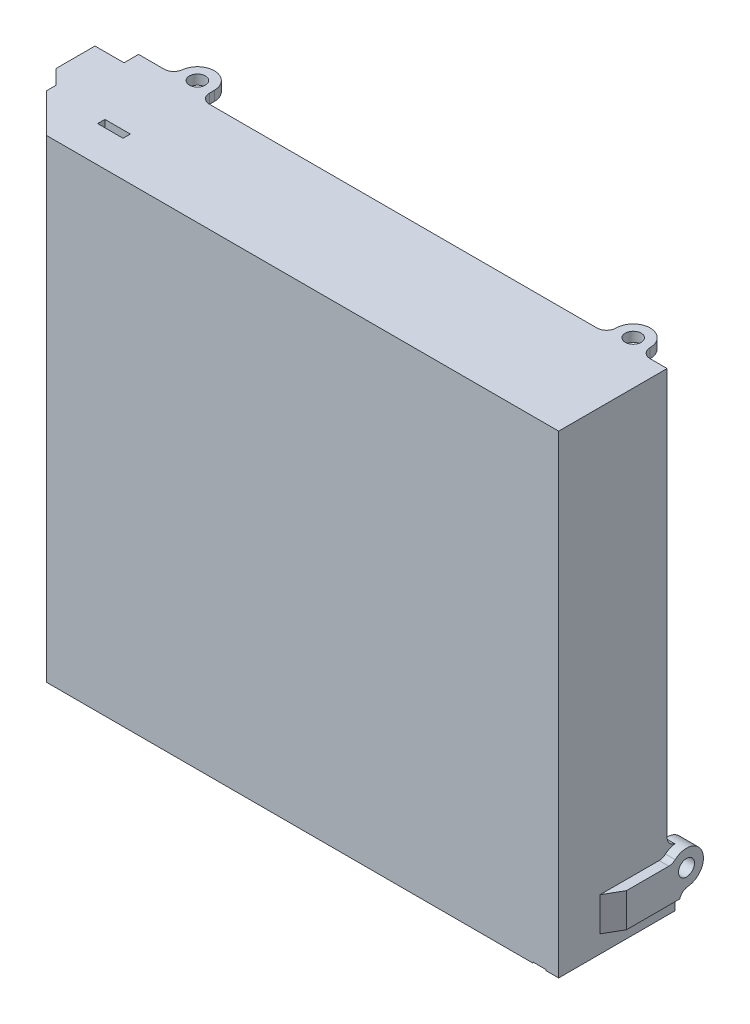
SolidWorks part; units mm, degrees
ref_plane "前视基准面" through (0, 0, 0) normal (0, 0, 1) x (1, 0, 0)
ref_plane "上视基准面" through (0, 0, 0) normal (0, 1, 0) x (1, 0, 0)
ref_plane "右视基准面" through (0, 0, 0) normal (1, 0, 0) x (0, 0, -1)
other "Configuration Table"
sketch "草图1" plane through (0, 0, 0) normal (0, 1, 0) x (1, 0, 0)
  line L1 (0, 0) -> (114.75, 0)
  line L2 (0, 0) -> (0, 22)
  line L3 (0, 22) -> (114.75, 22)
  line L4 (114.75, 0) -> (114.75, 22)
  line L5 (0, 0) -> (114.75, 22) construction
  line L6 (0, 22) -> (114.75, 0) construction
  point P4 (57.375, 11)
  dimension "D1" = 114.75
  dimension "D2" = 22
extrude "凸台-拉伸1" add sketch "草图1" along normal blind 2
sketch "草图2" plane through (0, 2, 0) normal (0, 1, 0) x (1, 0, 0)
  line L0 (16.75, 23.4) -> (16.75, 22) construction
  line L1 (114.75, 22) -> (0, 22) construction
  line L2 (0, 22) -> (0, 0) construction
  line L3 (0, 0) -> (114.75, 0) construction
  line L4 (20.25, 23.4) -> (20.25, 22)
  line L5 (13.25, 23.4) -> (13.25, 22)
  line L6 (107.75, 22) -> (107.75, 22.4) construction
  line L7 (104.25, 22) -> (104.25, 22.4)
  line L8 (111.25, 22) -> (111.25, 22.4)
  circle A0 centre (16.75, 23.4) radius 1.65
  arc A1 (20.25, 23.4) -> (13.25, 23.4) centre (16.75, 23.4) ccw
  arc A2 (13.25, 22) -> (20.25, 22) centre (16.75, 22) ccw
  arc A3 (104.25, 22) -> (111.25, 22) centre (107.75, 22) ccw
  arc A4 (111.25, 22.4) -> (104.25, 22.4) centre (107.75, 22.4) ccw
  circle A5 centre (107.75, 22.4) radius 1.65
  point P6 (16.75, 22.7)
  point P16 (107.75, 22.2)
  point P23 (107.6556, 23.4)
  point P24 (107.6398, 22.6248)
  dimension "D1" = 16.75
  dimension "D2" = 3.3
  dimension "D3" = 23.4
  dimension "D4" = 3.5
  dimension "D5" = 1
  dimension "D7" = 3.5
  dimension "D6" = 91
extrude "凸台-拉伸2" add sketch "草图2" against normal up to surface (2 mm away) up to face at (57.375, 0, -11)
sketch "草图3" plane through (0, 2, 0) normal (0, 1, 0) x (1, 0, 0)
  circle A0 centre (16.75, 23.4) radius 1.65
  circle A1 centre (107.75, 22.4) radius 1.65
extrude "切除-拉伸1" cut sketch "草图3" against normal blind 10
sketch "草图4" plane through (0, 0, 0) normal (0, -1, 0) x (1, 0, 0)
  line L0 (0, -22) -> (0, 0) construction
  line L1 (114.75, 0) -> (21.75, 0)
  line L2 (114.75, 0) -> (114.75, -17)
  line L3 (114.75, -17) -> (21.75, -17)
  line L4 (21.75, 0) -> (21.75, -17)
  line L5 (114.75, 0) -> (21.75, -17) construction
  line L6 (114.75, -17) -> (21.75, 0) construction
  point P4 (68.25, -8.5)
  dimension "D1" = 21.75
  dimension "D2" = 17
extrude "凸台-拉伸3" add sketch "草图4" along normal blind 1
sketch "草图5" plane through (0, 0, 0) normal (0, -1, 0) x (1, 0, 0)
  line L1 (0, -22) -> (6, -22)
  line L2 (0, -22) -> (0, -19)
  line L3 (0, -19) -> (6, -19)
  line L4 (6, -22) -> (6, -19)
  line L5 (0, -22) -> (6, -19) construction
  line L6 (0, -19) -> (6, -22) construction
  point P4 (3, -20.5)
  dimension "D1" = 3
  dimension "D2" = 6
extrude "切除-拉伸2" cut sketch "草图5" against normal up to next
sketch "草图6" plane through (0, 0, 0) normal (0, -1, 0) x (1, 0, 0)
  line L0 (0, 0) -> (21.75, 0) construction
  line L1 (14.15, -5.4) -> (19.4, -5.4)
  line L2 (14.15, -5.4) -> (14.15, -6.9)
  line L3 (14.15, -6.9) -> (19.4, -6.9)
  line L4 (19.4, -5.4) -> (19.4, -6.9)
  line L5 (14.15, -5.4) -> (19.4, -6.9) construction
  line L6 (14.15, -6.9) -> (19.4, -5.4) construction
  line L7 (0, -19) -> (0, 0) construction
  point P4 (16.775, -6.15)
  dimension "D1" = 6.9
  dimension "D2" = 1.5
  dimension "D3" = 14.15
  dimension "D4" = 5.25
extrude "切除-拉伸3" cut sketch "草图6" against normal up to next
sketch "草图7" plane through (0, 0, 0) normal (0, -1, 0) x (1, 0, 0)
  line L0 (14.15, -6.9) -> (19.4, -6.9) construction
  line L1 (21.75, 0) -> (16.75, 0)
  line L2 (21.75, 0) -> (21.75, -17)
  line L3 (21.75, -17) -> (16.75, -17)
  line L4 (16.75, 0) -> (16.75, -5.4)
  line L5 (21.75, 0) -> (16.75, -17) construction
  line L6 (21.75, -17) -> (16.75, 0) construction
  line L7 (19.4, -6.9) -> (19.4, -5.4) construction
  line L8 (19.4, -5.4) -> (14.15, -5.4) construction
  line L9 (16.75, -6.9) -> (19.4, -6.9)
  line L10 (19.4, -6.9) -> (19.4, -5.4)
  line L11 (19.4, -5.4) -> (16.75, -5.4)
  line L12 (16.75, -6.9) -> (16.75, -17)
  point P4 (19.25, -8.5)
  point P6 (21.75, -17)
  dimension "D1" = 5
extrude "凸台-拉伸4" add sketch "草图7" along normal blind 0.5
sketch "草图8" plane through (0, 0, 0) normal (0, -1, 0) x (1, 0, 0)
  line L1 (0, 0) -> (3, 0)
  line L2 (0, 0) -> (0, -10.9)
  line L3 (0, -10.9) -> (3, -10.9)
  line L4 (3, 0) -> (3, -10.9)
  line L5 (0, 0) -> (3, -10.9) construction
  line L6 (0, -10.9) -> (3, 0) construction
  line L7 (6, -19) -> (0, -19) construction
  point P4 (1.5, -5.45)
  dimension "D1" = 8.1
  dimension "D2" = 3
extrude "切除-拉伸4" cut sketch "草图8" against normal up to next
chamfer "倒角1" distance 3 angle 45 1 edges at (3, 1, -10.9)
chamfer "倒角2" distance 6 angle 45 1 edges at (3, 1, 0)
sketch "草图9" plane through (114.75, 0, 0) normal (1, 0, 0) x (0, 0, -1)
  line L1 (0, 2) -> (22, 2)
  line L2 (0, 2) -> (0, -95.8)
  line L3 (0, -95.8) -> (22, -95.8)
  line L4 (22, 2) -> (22, -95.8)
  line L5 (0, 2) -> (22, -95.8) construction
  line L6 (0, -95.8) -> (22, 2) construction
  point P4 (11, -46.9)
  point P6 (0, 0)
  point P8 (22, 2)
  dimension "D1" = 97.8
extrude "凸台-拉伸5" add sketch "草图9" along normal blind 2
sketch "草图10" plane through (0, 0, -17) normal (0, 0, -1) x (-1, 0, 0)
  line L1 (-114.75, 0) -> (-113.75, 0)
  line L2 (-114.75, 0) -> (-114.75, -95.8)
  line L3 (-114.75, -95.8) -> (-113.75, -95.8)
  line L4 (-113.75, 0) -> (-113.75, -95.8)
  line L5 (-114.75, 0) -> (-113.75, -95.8) construction
  line L6 (-114.75, -95.8) -> (-113.75, 0) construction
  point P4 (-114.25, -47.9)
  point P6 (-114.75, -95.8)
  dimension "D1" = 1
extrude "凸台-拉伸6" add sketch "草图10" against normal up to surface (17 mm away) up to face at (55.8, -19.06, 0)
fillet "圆角2" radius 3 1 edges at (114.75, 0, -19.5)
sketch "草图11" plane through (0, -95.8, 0) normal (0, -1, 0) x (1, 0, 0)
  line L0 (116.75, -22) -> (114.75, -22) construction
  line L1 (115.35, -22) -> (113.75, -22)
  line L2 (115.35, -22) -> (115.35, 0)
  line L3 (115.35, 0) -> (113.75, 0)
  line L4 (113.75, -22) -> (113.75, 0)
  line L5 (115.35, -22) -> (113.75, 0) construction
  line L6 (115.35, 0) -> (113.75, -22) construction
  line L7 (116.75, 0) -> (116.75, -22) construction
  point P4 (114.55, -11)
  dimension "D1" = 1.4
extrude "切除-拉伸6" cut sketch "草图11" against normal blind 1.6
sketch "草图12" plane through (113.75, 0, 0) normal (-1, 0, 0) x (0, 0, 1)
  line L1 (-19, -90.175) -> (-12, -90.175)
  line L2 (-19, -90.175) -> (-19, -87.175)
  line L3 (-19, -87.175) -> (-12, -87.175)
  line L4 (-12, -90.175) -> (-12, -87.175)
  line L5 (-19, -90.175) -> (-12, -87.175) construction
  line L6 (-19, -87.175) -> (-12, -90.175) construction
  line L7 (-22, -95.8) -> (0, -95.8) construction
  line L8 (-22, -94.2) -> (-22, -3) construction
  point P4 (-15.5, -88.675)
  dimension "D1" = 7.125
  dimension "D2" = 3
  dimension "D3" = 3
  dimension "D4" = 7
extrude "切除-拉伸7" cut sketch "草图12" against normal up to next
sketch "草图13" plane through (116.75, 0, 0) normal (1, 0, 0) x (0, 0, -1)
  line L0 (22, -95.8) -> (22, 2) construction
  line L1 (0, -95.8) -> (22, -95.8) construction
  line L2 (19, -87.175) -> (19, -90.175) construction
  line L3 (12, -87.175) -> (19, -87.175) construction
  line L4 (19, -87.175) -> (19, -88.1057)
  line L5 (18.9014, -87.175) -> (19, -87.175)
  circle A0 centre (22.4, -87.275) radius 1.65
  arc A1 (19, -88.1057) -> (18.9014, -87.175) centre (22.4, -87.275) ccw
  dimension "D1" = 3.3
  dimension "D2" = 0.4
  dimension "D3" = 7
  dimension "D4" = 8.525
extrude "凸台-拉伸7" add sketch "草图13" against normal up to surface (2 mm away) up to face at (114.75, -68.6375, -18.75)
sketch "草图14" plane through (116.75, 0, 0) normal (1, 0, 0) x (0, 0, -1)
  line L0 (12, -87.175) -> (19, -87.175) construction
  line L1 (21, -85.175) -> (10, -85.175)
  line L2 (21, -85.175) -> (21, -92.175)
  line L3 (21, -92.175) -> (10, -92.175)
  line L4 (10, -85.175) -> (10, -92.175)
  line L5 (21, -85.175) -> (10, -92.175) construction
  line L6 (21, -92.175) -> (10, -85.175) construction
  line L7 (19, -90.175) -> (12, -90.175) construction
  line L8 (12, -90.175) -> (12, -87.175) construction
  line L9 (19, -87.175) -> (19, -90.175) construction
  point P4 (15.5, -88.675)
  dimension "D1" = 2
  dimension "D2" = 2
  dimension "D3" = 2
  dimension "D4" = 2
extrude "凸台-拉伸8" add sketch "草图14" along normal blind 2
chamfer "倒角3" distance 2 angle 60 1 edges at (116.75, -88.675, -10) first distance on face at (117.75, -88.675, -10)
sketch "草图15" plane through (116.75, 0, 0) normal (1, 0, 0) x (0, 0, -1)
  circle A0 centre (22.4, -87.275) radius 1.65
  circle A1 centre (22.4, -87.275) radius 3.5
extrude "凸台-拉伸9" add sketch "草图15" along normal up to surface (2 mm away) up to face at (118.75, -88.675, -15.5)
sketch "草图16" plane through (118.75, 0, 0) normal (1, 0, 0) x (0, 0, -1)
  circle A0 centre (22.4, -87.275) radius 1.65
  arc A1 (21, -88.1482) -> (21, -86.4018) centre (22.4, -87.275) ccw construction
extrude "切除-拉伸8" cut sketch "草图16" against normal up to next
sketch "草图17" plane through (0, 0, -22) normal (0, 0, -1) x (-1, 0, 0)
  line L4 (-20.25, 2) -> (-104.25, 2)
  line L5 (-104.25, 2) -> (-104.25, 0)
  line L6 (-116.75, 2) -> (-116.75, -83.7979)
  line L7 (-116.75, -83.7979) -> (-114.75, -83.7979)
  line L8 (-114.75, -83.7979) -> (-114.75, -3)
  line L9 (-111.75, 0) -> (-111.25, 0)
  line L10 (-111.25, 0) -> (-111.25, 2)
  line L11 (-111.25, 2) -> (-116.75, 2)
  line L12 (-116.75, 2) -> (-116.75, -83.7979)
  line L13 (-116.75, -83.7979) -> (-114.75, -83.7979)
  line L14 (-114.75, -83.7979) -> (-114.75, -3)
  line L15 (-111.75, 0) -> (-111.25, 0)
  line L16 (-111.25, 0) -> (-111.25, 2)
  line L17 (-111.25, 2) -> (-116.75, 2)
  line L18 (-104.25, 0) -> (-20.25, 0)
  line L19 (-20.25, 0) -> (-20.25, 2)
  line L20 (-20.25, 2) -> (-104.25, 2)
  line L21 (-104.25, 2) -> (-104.25, 0)
  line L22 (-104.25, 0) -> (-20.25, 0)
  line L23 (-20.25, 0) -> (-20.25, 2)
  arc A1 (-111.75, 0) -> (-114.75, -3) centre (-111.75, -3) ccw
  arc A2 (-111.75, 0) -> (-114.75, -3) centre (-111.75, -3) ccw
  dimension "D1" = 0
  dimension "D2" = 0
extrude "切除-拉伸9" cut sketch "草图17" against normal blind 1.6
fillet "圆角3" radius 2 2 edges at (115.75, -90.7521, -22) (115.75, -83.7979, -20.4)
fillet "圆角4" radius 2 6 edges at (117.75, -85.175, -19.6) (117.75, -90.4828, -21) (20.25, 1, -20.4) (13.25, 1, -22) (104.25, 1, -20.4) (111.25, 1, -20.4)
sketch "草图18" plane through (0, 0, 0) normal (0, 0, 1) x (1, 0, 0)
  line L1 (9, 2) -> (116.75, 2)
  line L2 (9, 2) -> (9, -95.8)
  line L3 (9, -95.8) -> (116.75, -95.8)
  line L4 (116.75, 2) -> (116.75, -95.8)
  line L5 (9, 2) -> (116.75, -95.8) construction
  line L6 (9, -95.8) -> (116.75, 2) construction
  point P4 (62.875, -46.9)
extrude "凸台-拉伸10" add sketch "草图18" along normal blind 2
sketch "草图19" plane through (0, 2, 0) normal (0, 1, 0) x (1, 0, 0)
  line L0 (9, 0) -> (11, -2)
  line L1 (116.75, -2) -> (9, -2) construction
  line L2 (11, -2) -> (9, -2)
  line L3 (9, -2) -> (9, 0)
extrude "切除-拉伸10" cut sketch "草图19" against normal up to next
sketch "草图20" plane through (0, -94.2, 0) normal (0, -1, 0) x (1, 0, 0)
  line L0 (11, 2) -> (116.75, 2) construction
  line L1 (116.75, 2) -> (116.75, -22) construction
  circle A0 centre (112.75, -1.5) radius 1.25
  circle A1 centre (112.75, -1.5) radius 3.3
  dimension "D1" = 3.5
  dimension "D2" = 4
  dimension "D3" = 6.6
  dimension "D4" = 2.5
extrude "凸台-拉伸11" add sketch "草图20" against normal blind 5 from offset 1.5 offset against normal yes
sketch "草图21" plane through (0, -94.2, 0) normal (0, -1, 0) x (1, 0, 0)
  circle A0 centre (112.75, -1.5) radius 1.25
  arc A1 (113.75, -0.75) -> (113.75, -2.25) centre (112.75, -1.5) ccw construction
extrude "切除-拉伸11" cut sketch "草图21" against normal up to surface (6.5 mm away) up to face at (112.2027, -87.7, -1.7914)
fillet "圆角5" radius 1 2 edges at (113.75, -90.2, -4.6448) (109.8106, -90.2, 0)
sketch "草图23" plane through (0, -92.7, 0) normal (0, -1, 0) x (1, 0, 0)
  line L0 (113.75, -17) -> (114.75, -17) construction
  line L1 (113.75, 0) -> (114.45, 0)
  line L2 (113.75, 0) -> (113.75, -17)
  line L3 (113.75, -17) -> (114.45, -17)
  line L4 (114.45, 0) -> (114.45, -17)
  line L5 (113.75, 0) -> (114.45, -17) construction
  line L6 (113.75, -17) -> (114.45, 0) construction
  line L7 (116.75, 2) -> (116.75, -22) construction
  point P4 (114.1, -8.5)
  dimension "D1" = 2.3
extrude "切除-拉伸12" cut sketch "草图23" along normal up to surface (3.1 mm away) up to face at (80.7, -95.8, -6.6667)
sketch "草图24" plane through (0, -95.8, 0) normal (0, -1, 0) x (1, 0, 0)
  circle A0 centre (112.75, -1.5) radius 3.75
  dimension "D1" = 7.5
extrude "切除-拉伸14" cut sketch "草图24" against normal blind 0.2
sketch "草图25" plane through (0, -94.2, 0) normal (0, -1, 0) x (1, 0, 0)
  line L0 (115.35, 0) -> (115.35, -4.2023) construction
  line L1 (114.45, 0) -> (115.35, 0)
  line L2 (114.45, 0) -> (114.45, -3.7)
  line L3 (114.45, -3.7) -> (115.35, -3.7)
  line L4 (115.35, 0) -> (115.35, -3.7)
  line L5 (114.45, 0) -> (115.35, -3.7) construction
  line L6 (114.45, -3.7) -> (115.35, 0) construction
  circle A0 centre (112.75, -1.5) radius 1.25 construction
  point P4 (114.9, -1.85)
  dimension "D1" = 2.2
extrude "切除-拉伸15" cut sketch "草图25" against normal up to surface (1.5 mm away) up to face at (112.75, -92.7, -2.75)
fillet "圆角6" radius 1 1 edges at (114.45, -93.45, -3.7)
